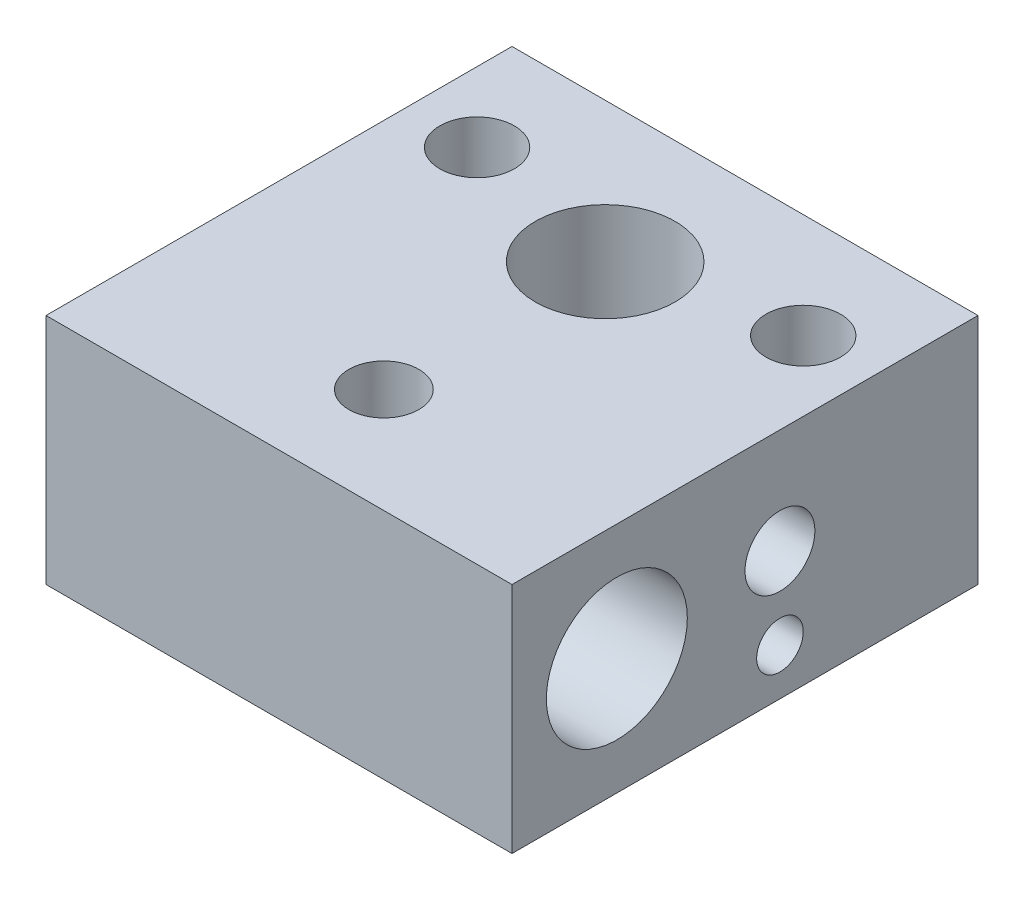
SolidWorks part; units mm, degrees
ref_plane "Front Plane" through (0, 0, 0) normal (0, 0, 1) x (1, 0, 0)
ref_plane "Top Plane" through (0, 0, 0) normal (0, 1, 0) x (1, 0, 0)
ref_plane "Right Plane" through (0, 0, 0) normal (1, 0, 0) x (0, 0, -1)
sketch "Sketch1" plane through (0, 0, 0) normal (0, 1, 0) x (1, 0, 0)
  line L1 (-10, -10) -> (10, -10)
  line L2 (-10, -10) -> (-10, 10)
  line L3 (-10, 10) -> (10, 10)
  line L4 (10, -10) -> (10, 10)
  line L5 (-10, -10) -> (10, 10) construction
  line L6 (-10, 10) -> (10, -10) construction
  point P0 (0, 0)
  dimension "D1" = 20
  dimension "D2" = 20
extrude "Boss-Extrude1" add sketch "Sketch1" against normal blind 10
sketch "Sketch2" plane through (0, 0, 0) normal (0, 1, 0) x (1, 0, 0)
  line L0 (0, 10) -> (0, -10) construction
  line L1 (10, 10) -> (-10, 10) construction
  line L2 (-10, -10) -> (10, -10) construction
  line L3 (-10, 0) -> (10, 0) construction
  line L4 (-10, 10) -> (-10, -10) construction
  line L5 (10, -10) -> (10, 10) construction
  circle A0 centre (0, 4) radius 3
  circle A1 centre (0, -5.5) radius 1.5
  dimension "D2" = 6
  dimension "D4" = 3
  dimension "D1" = 4
  dimension "D3" = 5.5
extrude "Cut-Extrude1" cut sketch "Sketch2" against normal through all contours A0
sketch "Sketch3" plane through (0, 0, 0) normal (0, 1, 0) x (1, 0, 0)
  line L0 (-10, 0) -> (10, 0) construction
  line L1 (0, 10) -> (0, -10) construction
  circle A0 centre (7, 5.5) radius 1.6
  dimension "D3" = 3.2
  dimension "D1" = 5.5
  dimension "D2" = 7
extrude "Cut-Extrude2" cut sketch "Sketch3" against normal through all contours A0
mirror "Mirror1" about plane through (0, 0, 0) normal (1, 0, 0) of "Cut-Extrude2"
chamfer "Chamfer1" distance 1 angle 45 1 edges at (7, -10, -3.9)
chamfer "Chamfer2" distance 1 angle 45 1 edges at (-7, -10, -3.9)
sketch "Sketch4" plane through (10, 0, 0) normal (1, 0, 0) x (0, 0, -1)
  line L0 (-10, -5) -> (10, -5) construction
  line L1 (-10, -10) -> (-10, 0) construction
  line L2 (10, -10) -> (10, 0) construction
  line L3 (0, 0) -> (0, -10) construction
  line L4 (-10, -10) -> (10, -10) construction
sketch "Sketch5" plane through (10, 0, 0) normal (1, 0, 0) x (0, 0, -1)
  line L0 (-10, -5) -> (10, -5) construction
  line L1 (0, 0) -> (0, -10) construction
  line L3 (-10, -10) -> (10, -10) construction
  circle A0 centre (-5.5, -5) radius 3.025
  circle A1 centre (1.5, -8) radius 1
  circle A2 centre (1.5, -4.5) radius 1.5
  dimension "D5" = 6.05
  dimension "D6" = 3
  dimension "D7" = 2
  dimension "D1" = 5.5
  dimension "D2" = 1.5
  dimension "D3" = 2
  dimension "D4" = 5.5
extrude "Cut-Extrude3" cut sketch "Sketch5" against normal through all
extrude "Cut-Extrude4" cut sketch "Sketch2<3>" against normal blind 4 contours A1
sketch "Sketch2<3>" plane through (0, 0, 0) normal (0, 1, 0) x (1, 0, 0) same geometry as "Sketch2"
